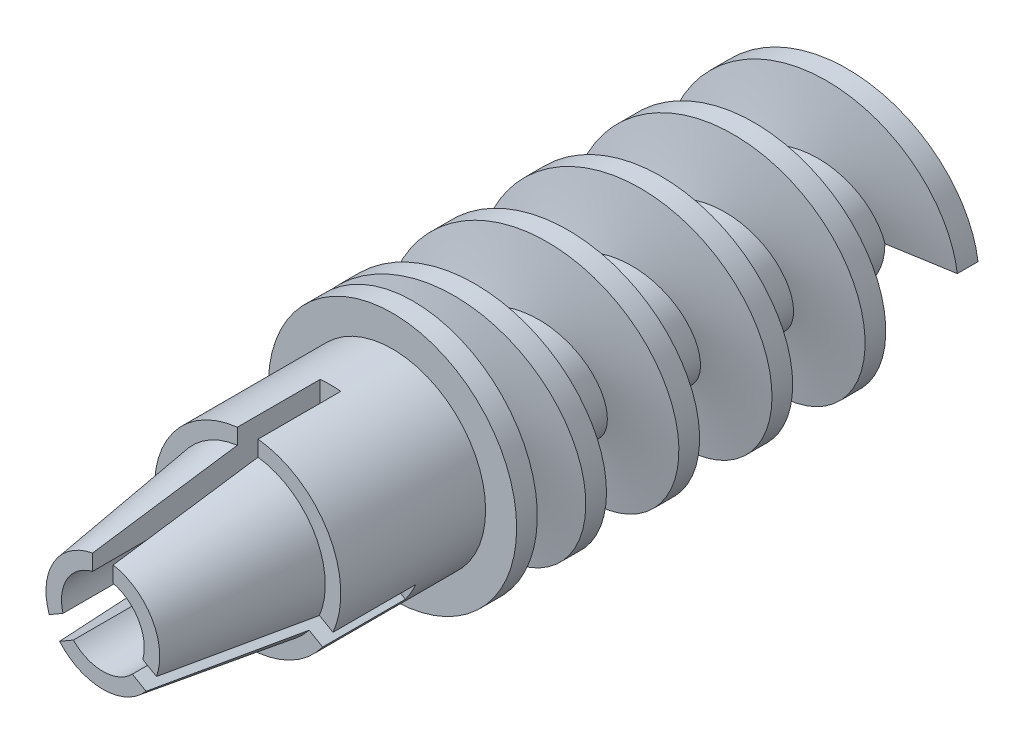
SolidWorks part; units mm, degrees
ref_plane "前视基准面" through (0, 0, 0) normal (0, 0, 1) x (1, 0, 0)
ref_plane "上视基准面" through (0, 0, 0) normal (0, 1, 0) x (1, 0, 0)
ref_plane "右视基准面" through (0, 0, 0) normal (1, 0, 0) x (0, 0, -1)
sketch "草图1" plane through (0, 0, 0) normal (0, 0, 1) x (1, 0, 0)
  circle A0 centre (0, 0) radius 2
  circle A1 centre (0, 0) radius 3
extrude "凸台-拉伸1" add sketch "草图1" against normal blind 32.5
sketch "草图3" plane through (0, 0, 0) normal (0, 0, 1) x (1, 0, 0)
  circle A0 centre (0, 0) radius 3
curve "螺旋线/涡状线1" pitch 4.5 height 31.5 radius 3 centre (0, 0, 0) axis (0, 0, -1) start towards (1, 0, 0)
sketch "草图4" plane through (0, 0, 0) normal (0, 1, 0) x (1, 0, 0)
  line L0 (3, 1) -> (3, -1)
  line L2 (6, 0.5) -> (6, -0.5)
  line L3 (3, -1) -> (6, -0.5)
  line L4 (3, 1) -> (6, 0.5)
sweep "扫描1" add profiles "草图4" path "螺旋线/涡状线1"
sketch "草图5" plane through (0, 0, -32.5) normal (0, 0, -1) x (-1, 0, 0)
  line L0 (0, 0) -> (-6, 0)
  line L1 (0, 0) -> (6, 0)
  arc A0 (-6, 0) -> (6, 0) centre (0, 0) ccw
extrude "切除-拉伸1" cut sketch "草图5" against normal blind 2
sketch "草图6" plane through (0, 0, 0) normal (0, 0, 1) x (1, 0, 0)
  circle A0 centre (0, 0) radius 7
  dimension "D1" = 14
extrude "切除-拉伸2" cut sketch "草图6" against normal blind 10.7 and the other way blind 2
sketch "草图8" plane through (0, 0, -10.7) normal (0, 0, 1) x (1, 0, 0)
  circle A0 centre (0, 0) radius 6
extrude "凸台-拉伸2" add sketch "草图8" along normal blind 1
sketch "草图9" plane through (0, 0, -9.7) normal (0, 0, 1) x (1, 0, 0)
  circle A0 centre (0, 0) radius 4.5
  dimension "D1" = 9
extrude "凸台-拉伸3" add sketch "草图9" along normal blind 7
sketch "草图10" plane through (0, 0, -2.7) normal (0, 0, 1) x (1, 0, 0)
  circle A0 centre (0, 0) radius 3.75
  dimension "D1" = 7.5
ref_plane "基准面1" through (0, 0, 4.3) normal (0, 0, 1) x (1, 0, 0)
sketch "草图11" plane through (0, 0, 4.3) normal (0, 0, 1) x (1, 0, 0)
  circle A0 centre (0, 0) radius 2.75
  dimension "D1" = 5.5
loft "放样1" add profiles "草图11", "草图10" connector at (2.7112, -0.4605, 4.3) connector at (3.7449, -0.1955, -2.7)
sketch "草图12" plane through (0, 0, 4.3) normal (0, 0, 1) x (1, 0, 0)
  circle A0 centre (0, 0) radius 2
  dimension "D1" = 4
extrude "切除-拉伸3" cut sketch "草图12" against normal through all
sketch "草图13" plane through (0, 0, 4.3) normal (0, 0, 1) x (1, 0, 0)
  line L0 (1.9271, -0.5352) -> (4.123, -1.8031)
  line L1 (-0.5, 1.9365) -> (-0.5, 4.4721)
  line L2 (3.623, -2.6691) -> (1.4271, -1.4013)
  line L3 (0.5, 4.4721) -> (0.5, 1.9365)
  line L4 (-1.4271, -1.4013) -> (-3.623, -2.6691)
  line L5 (-4.123, -1.8031) -> (-1.9271, -0.5352)
  arc A0 (-4.123, -1.8031) -> (-3.623, -2.6691) centre (0, 0) ccw
  arc A1 (-1.9271, -0.5352) -> (-1.4271, -1.4013) centre (0, 0) ccw
  arc A2 (3.623, -2.6691) -> (4.123, -1.8031) centre (0, 0) ccw
  arc A3 (1.4271, -1.4013) -> (1.9271, -0.5352) centre (0, 0) ccw
  arc A4 (0.5, 1.9365) -> (-0.5, 1.9365) centre (0, 0) ccw
  arc A5 (0.5, 4.4721) -> (-0.5, 4.4721) centre (0, 0) ccw
  point P18 (0, 0)
  dimension "D3" = 9
  dimension "D4" = 4
  dimension "D1" = 3
extrude "切除-拉伸4" cut sketch "草图13" against normal blind 11
